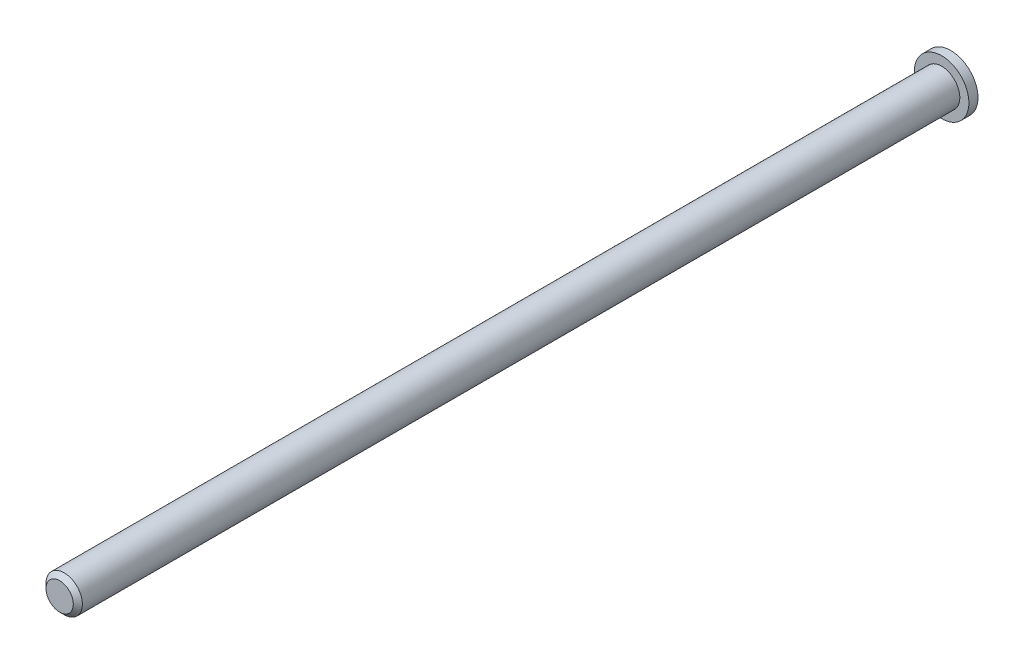
SolidWorks part; units mm, degrees
ref_plane "Front Plane" through (0, 0, 0) normal (0, 0, 1) x (1, 0, 0)
ref_plane "Top Plane" through (0, 0, 0) normal (0, 1, 0) x (1, 0, 0)
ref_plane "Right Plane" through (0, 0, 0) normal (1, 0, 0) x (0, 0, -1)
sketch "Sketch1" plane through (0, 0, 0) normal (0, 0, 1) x (1, 0, 0)
  circle A0 centre (0, 0) radius 1.5
  dimension "D1" = 3
extrude "Boss-Extrude1" add sketch "Sketch1" along normal blind 0.5
sketch "Sketch2" plane through (0, 0, 0.5) normal (0, 0, 1) x (1, 0, 0)
  circle A0 centre (0, 0) radius 1
  dimension "D1" = 2
extrude "Boss-Extrude2" add sketch "Sketch2" along normal blind 48.5
chamfer "Chamfer1" distance 0.25 angle 45 1 edges at (1, 0, 49)
